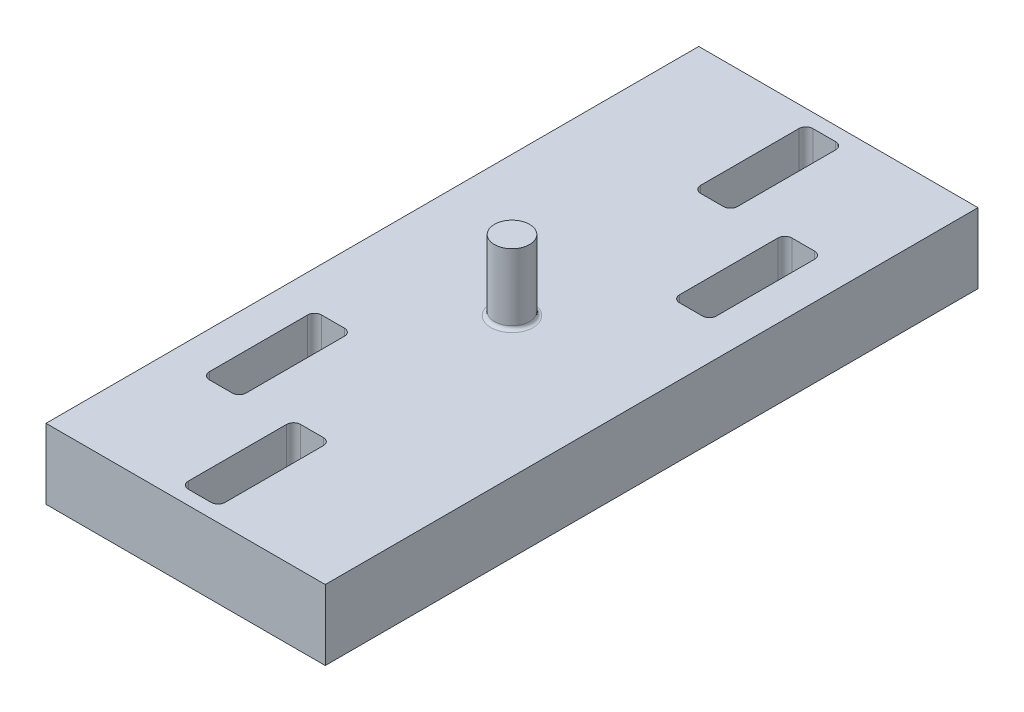
SolidWorks part; units mm, degrees
ref_plane "Front Plane" through (0, 0, 0) normal (0, 0, 1) x (1, 0, 0)
ref_plane "Top Plane" through (0, 0, 0) normal (0, 1, 0) x (1, 0, 0)
ref_plane "Right Plane" through (0, 0, 0) normal (1, 0, 0) x (0, 0, -1)
sketch "10" plane through (0, 0, 0) normal (0, 1, 0) x (1, 0, 0)
  line L0 (-15, 31.5) -> (15, 31.5) construction
  line L1 (-14.8938, 29.7182) -> (14.8938, 33.2818)
  line L2 (-14.8938, 29.7182) -> (-12, 15)
  line L3 (14.8938, 33.2818) -> (12, 48)
  line L4 (-12, 15) -> (0, 15)
  line L5 (12, 48) -> (0, 48)
  line L6 (0, 48) -> (0, 63)
  line L7 (0, 15) -> (0, 0)
  point P4 (0, 31.5)
  point P5 (0, 31.5)
  dimension "D1" = 15
  dimension "D2" = 12
  dimension "D3" = 15
  dimension "D4" = 30
  dimension "D5" = 30
  dimension "D6" = 15
  dimension "D7" = 0
  dimension "D8" = 0
  dimension "D9" = 31.5
sketch "01" plane through (0, 0, 0) normal (0, 1, 0) x (1, 0, 0)
  line L0 (-15, 31.5) -> (15, 31.5) construction
  line L1 (-9.3393, 19.7621) -> (9.3393, 43.2379)
  line L2 (-9.3393, 19.7621) -> (-12, 5)
  line L3 (9.3393, 43.2379) -> (12, 58)
  line L4 (-12, 5) -> (0, 5)
  line L5 (12, 58) -> (0, 58)
  line L6 (0, 58) -> (0, 73)
  line L7 (0, 5) -> (0, -10)
  point P4 (0, 31.5)
  point P5 (0, 31.5)
  dimension "D1" = 30
  dimension "D2" = 15
  dimension "D3" = 12
  dimension "D4" = 15
  dimension "D5" = 30
  dimension "D6" = 0
  dimension "D7" = 41.5
  dimension "D8" = 0
  dimension "D9" = 15
sketch "Sketch2" plane through (0, 0, 0) normal (0, 1, 0) x (1, 0, 0)
  line L1 (-19.8938, 78) -> (0, 78)
  line L2 (-19.8938, 78) -> (-19.8938, -15)
  line L3 (-19.8938, -15) -> (0, -15)
  line L9 (-15, 31.5) -> (15, 31.5) construction
  line L12 (0, 78) -> (0, 76)
  line L16 (0, -15) -> (0, -13)
  line L21 (0, 60) -> (0, 3)
  line L22 (-2.625, 0.5) -> (0, 3) construction
  line L23 (0, 3) -> (-2.625, 3) construction
  line L24 (-2.625, 3) -> (-2.625, 0.5) construction
  line L25 (0, 3) -> (2.625, 0.5) construction
  line L26 (0, 3) -> (2.625, 3) construction
  line L27 (2.625, 3) -> (2.625, 0.5) construction
  line L28 (0, 60) -> (-2.625, 60)
  line L29 (-2.625, 3) -> (0, 3)
  line L30 (-2.625, 3) -> (-2.625, -13)
  line L31 (-2.625, -13) -> (0, -13)
  line L33 (-2.625, 60) -> (-2.625, 76)
  line L34 (-2.625, 76) -> (0, 76)
  circle A7 centre (-14.8938, 29.7182) radius 5 construction
  circle A19 centre (0, -10.5) radius 2.5 construction
  circle A20 centre (0, 0.5) radius 2.5 construction
  circle A21 centre (0, -10.5) radius 2.625 construction
  circle A22 centre (0, 0.5) radius 2.625 construction
  circle A23 centre (0, 73.5) radius 2.5 construction
  circle A24 centre (0, 73.5) radius 2.625 construction
  circle A27 centre (0, 62.5) radius 2.5 construction
  circle A28 centre (0, 62.5) radius 2.625 construction
  dimension "D2" = 5.25
  dimension "D3" = 5
  dimension "D4" = 5
  dimension "D5" = 5
  dimension "D8" = 5.25
  dimension "D7" = 10
  dimension "D15" = 5.25
  dimension "D16" = 5.25
  dimension "D6" = 5
  dimension "D9" = 2
  dimension "D10" = 19.8938
  dimension "D11" = 5
  dimension "D12" = 2
  dimension "D13" = 19.8938
  dimension "D14" = 57
extrude "Boss-Extrude1" add sketch "Sketch2" along normal blind 10 contours L2 L3 L16 L31 L30 L29 L21 L28 L33 L34 L12 L1
mirror "Mirror1" of "Boss-Extrude1"
sketch "Sketch4" plane through (0, 0, 0) normal (0, 1, 0) x (1, 0, 0)
  line L0 (-19.8938, 78) -> (-19.8938, -15) construction
  line L1 (-12, 4.5) -> (-12, 15.5) construction
  line L4 (-15, 31.5) -> (15, 31.5) construction
  line L5 (-15, 31.5) -> (15, 31.5) construction
  line L7 (0, 78) -> (0, -15) construction
  line L12 (-19.8938, -15) -> (19.8938, -15) construction
  line L13 (-19.8938, 78) -> (19.8938, 78) construction
  line L14 (-14.625, 18) -> (-14.625, 2)
  line L15 (-9.375, 18) -> (-9.375, 2)
  line L23 (-14.625, 18) -> (-9.375, 18)
  line L26 (-14.625, 2) -> (-9.375, 2)
  line L28 (13.2642, 2.125) -> (10.4043, 2.125) construction
  line L29 (9.375, 2) -> (9.375, 4.5) construction
  line L30 (14.625, 2) -> (9.375, 2) construction
  line L31 (14.625, 4.5) -> (14.625, 2) construction
  line L32 (9.375, 18) -> (9.375, 15.5) construction
  line L33 (14.625, 18) -> (9.375, 18) construction
  line L34 (14.625, 15.53) -> (14.625, 18) construction
  line L35 (9.375, 15.5) -> (9.375, 4.5) construction
  line L36 (14.625, 15.53) -> (14.625, 4.5) construction
  line L37 (14.625, 47.47) -> (14.625, 58.5)
  line L38 (9.375, 47.5) -> (9.375, 58.5)
  line L39 (14.625, 47.47) -> (14.625, 45)
  line L40 (14.625, 45) -> (9.375, 45)
  line L41 (9.375, 45) -> (9.375, 47.5)
  line L42 (14.625, 58.5) -> (14.625, 61)
  line L44 (9.375, 61) -> (9.375, 58.5)
  line L45 (9.375, 61) -> (14.625, 61)
  line L46 (-2.625, 3) -> (2.625, 3) construction
  circle A0 centre (-12, 4.5) radius 2.625 construction
  circle A1 centre (-12, 15.5) radius 2.625 construction
  circle A14 centre (-12, 4.5) radius 2.5 construction
  circle A15 centre (-12, 15.5) radius 2.5 construction
  circle A16 centre (12, 15.5) radius 2.5 construction
  circle A17 centre (12, 4.5) radius 2.5 construction
  circle A18 centre (12, 15.5) radius 2.625 construction
  circle A19 centre (12, 4.5) radius 2.625 construction
  circle A20 centre (12, 58.5) radius 2.625 construction
  circle A21 centre (12, 47.5) radius 2.625 construction
  circle A22 centre (12, 58.5) radius 2.5 construction
  circle A23 centre (12, 47.5) radius 2.5 construction
  point P7 (0, 0)
  point P11 (0, 0)
  point P17 (0, 0)
  dimension "D1" = 5.25
  dimension "D2" = 5.2688
  dimension "D6" = 5
  dimension "D4" = 1
  dimension "D3" = 16
extrude "Cut-Extrude1" cut sketch "Sketch4" along normal through all
sketch "Sketch5" plane through (0, 10, 0) normal (0, 1, 0) x (1, 0, 0)
  line L0 (-14.8938, 29.7182) -> (14.8938, 33.2818) construction
  circle A0 centre (0, 31.5) radius 2.5
  dimension "D1" = 5
extrude "Boss-Extrude2" add sketch "Sketch5" along normal blind 10
fillet "Fillet1" radius 0.5 1 edges at (0, 10, -34)
fillet "Fillet2" radius 1 16 edges at (2.625, 5, -60) (-2.625, 5, -60) (-2.625, 5, -76) (2.625, 5, -76) (14.625, 5, -61) (9.375, 5, -61) (9.375, 5, -45) (14.625, 5, -45) (2.625, 5, 13) (2.625, 5, -3) (-2.625, 5, -3) (-2.625, 5, 13) (-9.375, 5, -2) (-14.625, 5, -2) (-14.625, 5, -18) (-9.375, 5, -18)
